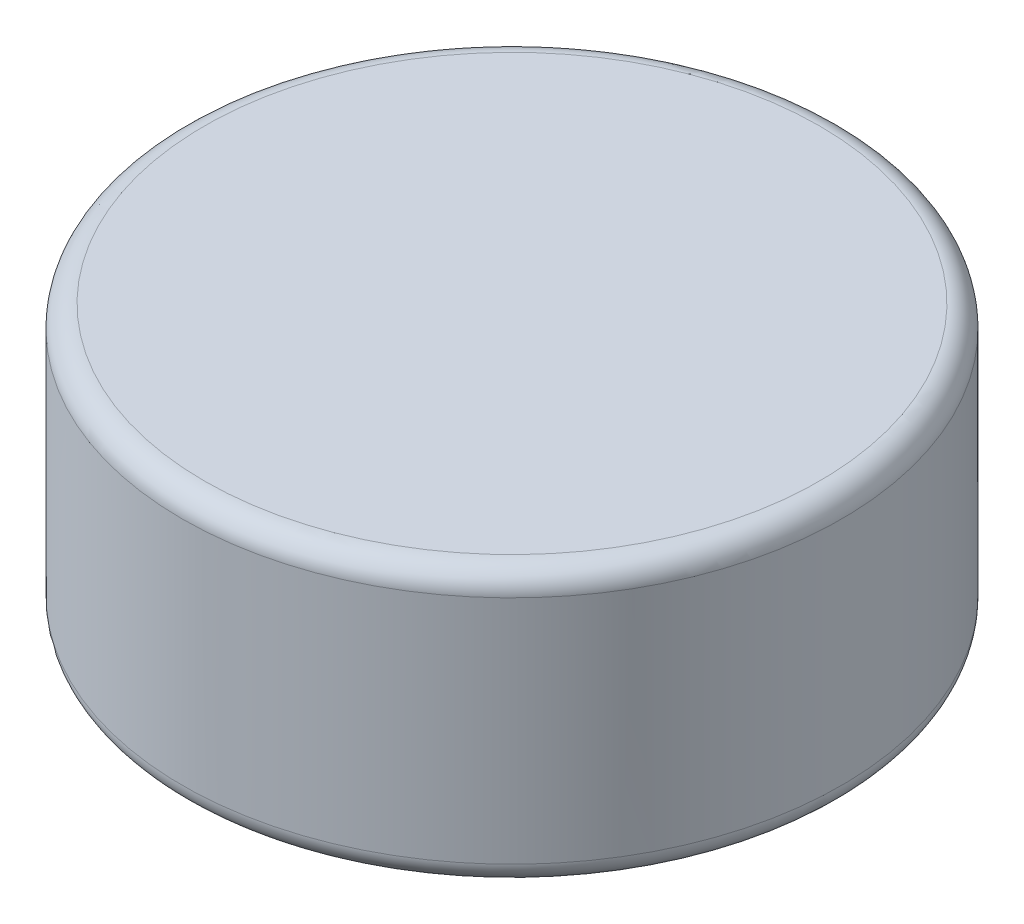
SolidWorks part; units mm, degrees
material "Chrome Stainless Steel"
ref_plane "Front Plane" through (0, 0, 0) normal (0, 0, 1) x (1, 0, 0)
ref_plane "Top Plane" through (0, 0, 0) normal (0, 1, 0) x (1, 0, 0)
ref_plane "Right Plane" through (0, 0, 0) normal (1, 0, 0) x (0, 0, -1)
sketch "Sketch1" plane through (0, 0, 0) normal (0, 0, 1) x (1, 0, 0)
  line L0 (0, 0) -> (0, 2.5) construction
  line L1 (0, 0) -> (3, 0)
  line L2 (3, 0) -> (3, 2.5)
  line L3 (3, 2.5) -> (0, 2.5)
  line L5 (0, 2.5) -> (0, 0)
  dimension "D1" = 2.5
  dimension "D2" = 6
revolve "Revolve1" add sketch "Sketch1" angle 360 about L0
fillet "Fillet1" radius 0.2 2 edges at (0, 0, -3) (0, 2.5, -3)
ref_axis "MAGNET" through (0, 2.625, 0) along (0, -1, 0)
